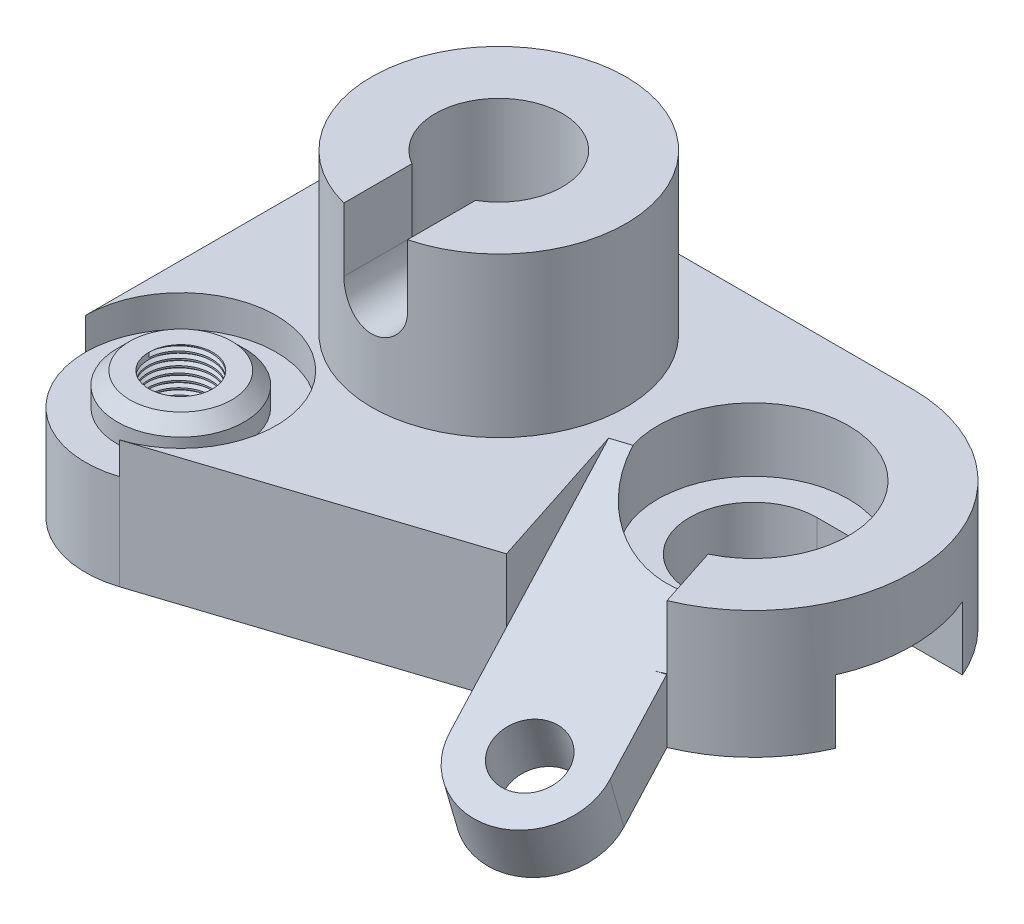
SolidWorks part; units mm, degrees
ref_plane "Front Plane" through (0, 0, 0) normal (0, 0, 1) x (1, 0, 0)
ref_plane "Top Plane" through (0, 0, 0) normal (0, 1, 0) x (1, 0, 0)
ref_plane "Right Plane" through (0, 0, 0) normal (1, 0, 0) x (0, 0, -1)
sketch "Sketch1" plane through (0, 0, 0) normal (0, 1, 0) x (1, 0, 0)
  line L0 (0, 0) -> (75, 0)
  line L1 (0, 0) -> (0, -55)
  line L2 (19.6332, -69.2665) -> (82.7221, -48.7775)
  arc A0 (82.7221, -48.7775) -> (75, 0) centre (75, -25) ccw
  arc A1 (0, -55) -> (19.6332, -69.2665) centre (15, -55) ccw
  dimension "D1" = 50
  dimension "D2" = 30
  dimension "D3" = 75
  dimension "D4" = 55
extrude "Boss-Extrude1" add sketch "Sketch1" along normal blind 20
sketch "Sketch2" plane through (0, 20, 0) normal (0, 1, 0) x (1, 0, 0)
  circle A0 centre (15, -55) radius 15
  circle A1 centre (15, -55) radius 10
  dimension "D1" = 30
  dimension "D2" = 20
extrude "Cut-Extrude1" cut sketch "Sketch2" against normal blind 5
sketch "Sketch3" plane through (0, 20, 0) normal (0, 1, 0) x (1, 0, 0)
  circle A0 centre (75, -25) radius 15
  dimension "D1" = 30
extrude "Cut-Extrude2" cut sketch "Sketch3" against normal blind 10
sketch "Sketch4" plane through (0, 10, 0) normal (0, 1, 0) x (1, 0, 0)
  circle A0 centre (75, -25) radius 10
  dimension "D1" = 20
extrude "Cut-Extrude3" cut sketch "Sketch4" against normal blind 10
sketch "Sketch6" plane through (0, 20, 0) normal (0, 1, 0) x (1, 0, 0)
  line L0 (35, -25) -> (0, -25) construction
  line L1 (0, 0) -> (0, -55) construction
  circle A0 centre (35, -25) radius 20
  circle A1 centre (35, -25) radius 10
  dimension "D2" = 40
  dimension "D3" = 20
  dimension "D1" = 35
extrude "Boss-Extrude2" add sketch "Sketch6" along normal blind 25
ref_plane "Plane1" through (0, 0, 45) normal (0, 0, 1) x (1, 0, 0)
sketch "Sketch7" plane through (0, 0, 45) normal (0, 0, 1) x (1, 0, 0)
  line L0 (15, 45) -> (15, 20) construction
  line L1 (19.6332, 20) -> (82.7221, 20) construction
  line L2 (40, 35) -> (40, 45)
  line L3 (55, 45) -> (15, 45) construction
  line L4 (30, 35) -> (30, 45)
  line L5 (45, 45) -> (25, 45) construction
  line L6 (30, 45) -> (40, 45)
  arc A0 (30, 35) -> (40, 35) centre (35, 35) ccw
  dimension "D3" = 5
  dimension "D1" = 20
  dimension "D2" = 15
extrude "Cut-Extrude7" cut sketch "Sketch7" against normal blind 20
sketch "Sketch8" plane through (0, 20, 0) normal (0, 1, 0) x (1, 0, 0)
  line L0 (30, -33.6603) -> (30, -25)
  line L1 (40, -33.6603) -> (40, -25)
  line L2 (40, -25) -> (30, -25)
  arc A1 (30, -33.6603) -> (40, -33.6603) centre (35, -25) ccw
extrude "Cut-Extrude8" cut sketch "Sketch8" against normal through all
ref_plane "Plane2" through (100, 0, 0) normal (1, 0, 0) x (0, 0, -1)
sketch "Sketch9" plane through (100, 0, 0) normal (1, 0, 0) x (0, 0, -1)
  line L0 (0, 0) -> (-55, 0) construction
  line L1 (-15, 0) -> (-35, 0)
  line L2 (-15, 0) -> (-15, 10)
  line L3 (-15, 10) -> (-35, 10)
  line L4 (-35, 0) -> (-35, 10)
  line L5 (-25, 10) -> (-25, 0) construction
  line L6 (-15, 5) -> (-35, 5) construction
  line L7 (0, 20) -> (0, 0) construction
  point P0 (-25, 5)
  dimension "D1" = 10
  dimension "D2" = 20
  dimension "D3" = 25
extrude "Cut-Extrude9" cut sketch "Sketch9" against normal up to next
chamfer "Chamfer1" distance 2 angle 45 1 edges at (15, 20, 65)
sketch "Sketch11" plane through (0, 20, 0) normal (0, 1, 0) x (1, 0, 0)
  circle A0 centre (15, -55) radius 5
  dimension "D1" = 10
extrude "Cut-Extrude10" cut sketch "Sketch11" against normal blind 17
thread "Thread1" pitch 1 method cut profile "Thread Profile1" start angle 0, offset 0, length 12, pitch 1, diameter 10
ref_plane "Plane3" through (10, 20, 55) normal (0, 0, 1) x (-1, 0, 0)
sketch "Thread Profile1" plane through (10, 20, 55) normal (0, 0, 1) x (-1, 0, 0)
  line L0 (0, 0) -> (0, 1) construction
  line L1 (0, 0) -> (0.5413, 0.3125)
  line L2 (0.5413, 0.3125) -> (0.5413, 0.4375)
  line L3 (0.5413, 0.4375) -> (0, 0.75)
  line L4 (0.5413, 0.375) -> (0, 0.375) construction
  line L11 (0, 0) -> (0, 0.75)
  point P2 (0, 0)
  dimension "Pitch" = 1
  dimension "Profile_Angle" = 60
  dimension "Profile_Land" = 0.125
  dimension "Profile_Height" = 0.5413
sketch "Sketch16" plane through (0, 20, 0) normal (0, 1, 0) x (1, 0, 0)
  line L0 (76.8602, -24.3959) -> (57.8384, -30.5735)
  line L1 (57.8384, -30.5735) -> (52.2208, -13.2761) construction
  line L2 (19.6332, -69.2665) -> (82.7221, -48.7775) construction
  line L3 (57.8384, -30.5735) -> (65.5604, -54.351)
  line L4 (65.5604, -54.351) -> (84.5586, -48.1005)
  line L5 (84.5586, -48.1005) -> (76.8602, -24.3959)
  circle A0 centre (35, -25) radius 20 construction
  arc A1 (82.7221, -48.7775) -> (75, 0) centre (75, -25) ccw construction
  point P6 (75, -25)
  point P15 (77.8538, -23.9301)
  point P16 (77.4545, -23.9301)
  dimension "D1" = 20
sketch "Sketch18" plane through (22.2222, 0, 68.4257) normal (0.3089, 0, 0.9511) x (0.9511, 0, -0.3089)
  line L0 (45.5664, 20) -> (45.5664, 10)
  line L1 (-2.7221, 20) -> (63.6104, 20) construction
  line L2 (45.5664, 10) -> (65.5664, 10)
  line L3 (65.5664, 10) -> (65.5664, 20)
  line L4 (65.5664, 20) -> (45.5664, 20)
  dimension "D1" = 20
  dimension "D2" = 10
ref_plane "Plane4" through (43.3382, 0, -14.0747) normal (0.9511, 0, -0.3089) x (-0.3089, 0, -0.9511)
sketch "Sketch19" plane through (43.3382, 0, -14.0747) normal (0.9511, 0, -0.3089) x (-0.3089, 0, -0.9511)
  line L0 (-71.9437, 10) -> (-46.9437, 20)
  line L1 (-71.9437, 10) -> (-71.9437, 20) construction
  line L2 (-71.9437, 20) -> (-71.9437, 10) construction
  line L3 (-71.9437, 10) -> (-71.9437, 20)
  line L4 (-71.9437, 20) -> (-46.9437, 20)
  dimension "D1" = 10
extrude "Cut-Extrude11" cut sketch "Sketch19" along normal blind 20 contours L0 L4 L3
sketch "Sketch20" plane through (4.1302, 33.4289, 12.7177) normal (0.1147, 0.9285, 0.3532) x (0.9934, -0.1072, -0.0408)
  line L0 (61.8384, -47.2432) -> (66.1689, -61.6045)
  line L1 (45.2141, 7.8891) -> (42.0384, 18.4207) construction
  line L2 (80.9868, -41.4693) -> (85.3173, -55.8306)
  line L3 (85.3173, -55.8306) -> (66.1689, -61.6045) construction
  line L4 (61.8384, -47.2432) -> (80.9868, -41.4693) construction
  line L5 (61.8384, -47.2432) -> (80.9868, -41.4693)
  arc A0 (66.1689, -61.6045) -> (85.3173, -55.8306) centre (75.7431, -58.7176) ccw
  dimension "D1" = 15
extrude "Boss-Extrude3" add sketch "Sketch20" against normal up to vertex up to point (19.6332, 0, 69.2665)
sketch "Sketch21" plane through (4.1302, 33.4289, 12.7177) normal (0.1147, 0.9285, 0.3532) x (0.9934, -0.1072, -0.0408)
  circle A0 centre (75.7431, -58.7176) radius 5
  dimension "D1" = 10
extrude "Cut-Extrude12" cut sketch "Sketch21" against normal up to next
sketch "Sketch22" plane through (0, 0, 45) normal (0, 0, 1) x (1, 0, 0)
  line L0 (55, 45) -> (55, 50.8637)
  line L1 (55, 50.8637) -> (65.5117, 56.6843)
  line L2 (65.5117, 56.6843) -> (65.5117, 61.684)
